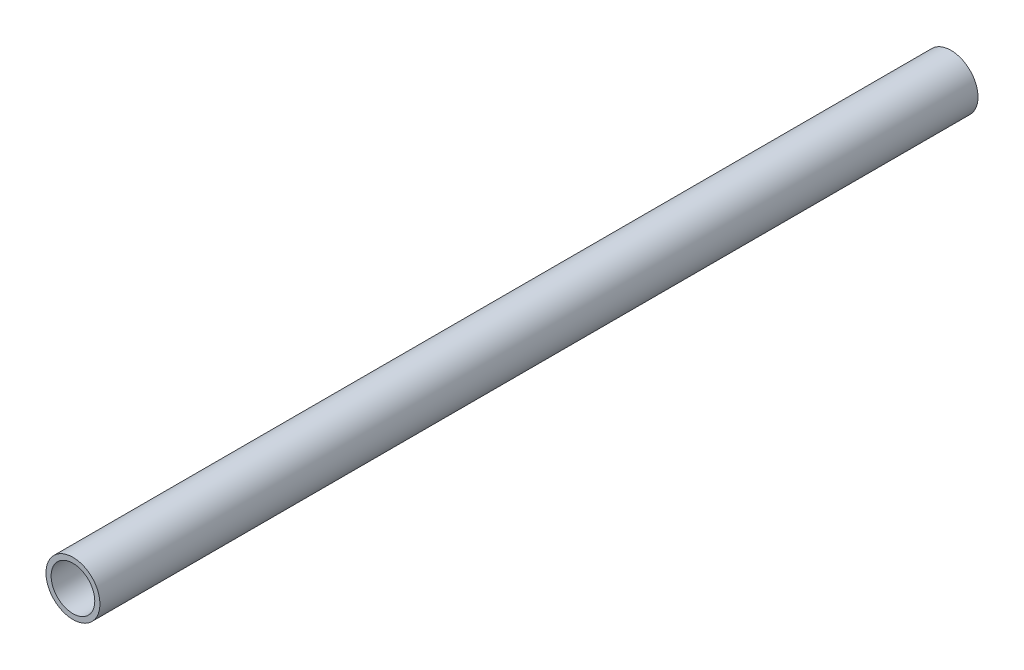
SolidWorks part; units mm, degrees
material "AISI 4130 Steel, annealed at 865C"
ref_plane "Front Plane" through (0, 0, 0) normal (0, 0, 1) x (1, 0, 0)
ref_plane "Top Plane" through (0, 0, 0) normal (0, 1, 0) x (1, 0, 0)
ref_plane "Right Plane" through (0, 0, 0) normal (1, 0, 0) x (0, 0, -1)
sketch "Sketch1" plane through (0, 0, 0) normal (0, 0, 1) x (1, 0, 0)
  circle A0 centre (0, 0) radius 6.477
  circle A1 centre (0, 0) radius 8.001
  dimension "D1" = 12.954
  dimension "D2" = 16.002
extrude "Boss-Extrude1" add sketch "Sketch1" along normal blind 260.35
sketch "Sketch2" plane through (0, 0, 0) normal (1, 0, 0) x (0, 0, -1)
  line L0 (0, 3.175) -> (-31.75, 3.175)
  line L1 (0, 55) -> (0, -55) construction
  line L2 (-31.75, -3.175) -> (0, -3.175)
  line L3 (-33.274, 1.651) -> (-33.274, -1.651)
  line L4 (0, -8.001) -> (0, 8.001) construction
  arc A0 (-33.274, 1.651) -> (-31.75, 3.175) centre (-31.75, 1.651) cw
  arc A1 (-31.75, -3.175) -> (-33.274, -1.651) centre (-31.75, -1.651) cw
  dimension "D5" = 31.75
  dimension "D6" = 33.274
  dimension "D1" = 33.274
  dimension "D2" = 31.75
  dimension "D3" = 6.35
  dimension "D4" = 3.175
